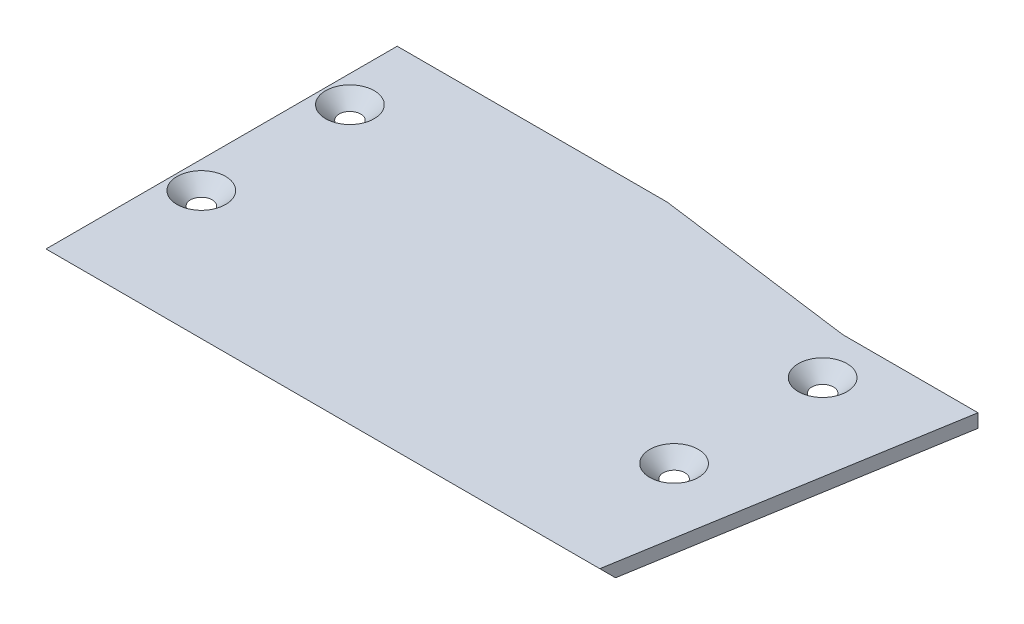
SolidWorks part; units mm, degrees
material "Titanium Ti-8Al-1Mo-1V"
ref_plane "Front Plane" through (0, 0, 0) normal (0, 0, 1) x (1, 0, 0)
ref_plane "Top Plane" through (0, 0, 0) normal (0, 1, 0) x (1, 0, 0)
ref_plane "Right Plane" through (0, 0, 0) normal (1, 0, 0) x (0, 0, -1)
sketch "Sketch1" plane through (0, 0, 0) normal (0, 1, 0) x (1, 0, 0)
  line L0 (0, 0) -> (0, 4)
  line L1 (0, 4) -> (40, 4)
  line L2 (40, 4) -> (70, 0)
  line L3 (70, 0) -> (90, 0)
  line L4 (90, 0) -> (82, -48)
  line L5 (82, -48) -> (0, -48)
  line L6 (0, -48) -> (0, 0)
  dimension "D1" = 48
  dimension "D2" = 20
  dimension "D3" = 30
  dimension "D4" = 82
  dimension "D5" = 40
  dimension "D6" = 4
extrude "Boss-Extrude1" add sketch "Sketch1" along normal blind 2
chamfer "Chamfer1" distance 2 angle 45 1 edges at (41, 0, 48)
sketch "Sketch2" plane through (0, 2, 0) normal (0, 1, 0) x (1, 0, 0)
  line L0 (0, 4) -> (0, -48) construction
  line L1 (90, 0) -> (70, 0) construction
  circle A0 centre (4, -7) radius 1.6
  circle A1 centre (4, -29) radius 1.6
  circle A2 centre (74, -7) radius 1.6
  circle A3 centre (74, -29) radius 1.6
  dimension "D2" = 3.2
  dimension "D5" = 3.2
  dimension "D1" = 4
  dimension "D3" = 7
  dimension "D4" = 22
  dimension "D7" = 70
  dimension "D6" = 2
extrude "Cut-Extrude1" cut sketch "Sketch2" against normal through all
chamfer "Chamfer2" distance 2 angle 45 4 edges at (74, 2, 8.6) (74, 2, 30.6) (4, 2, 8.6) (4, 2, 30.6)
